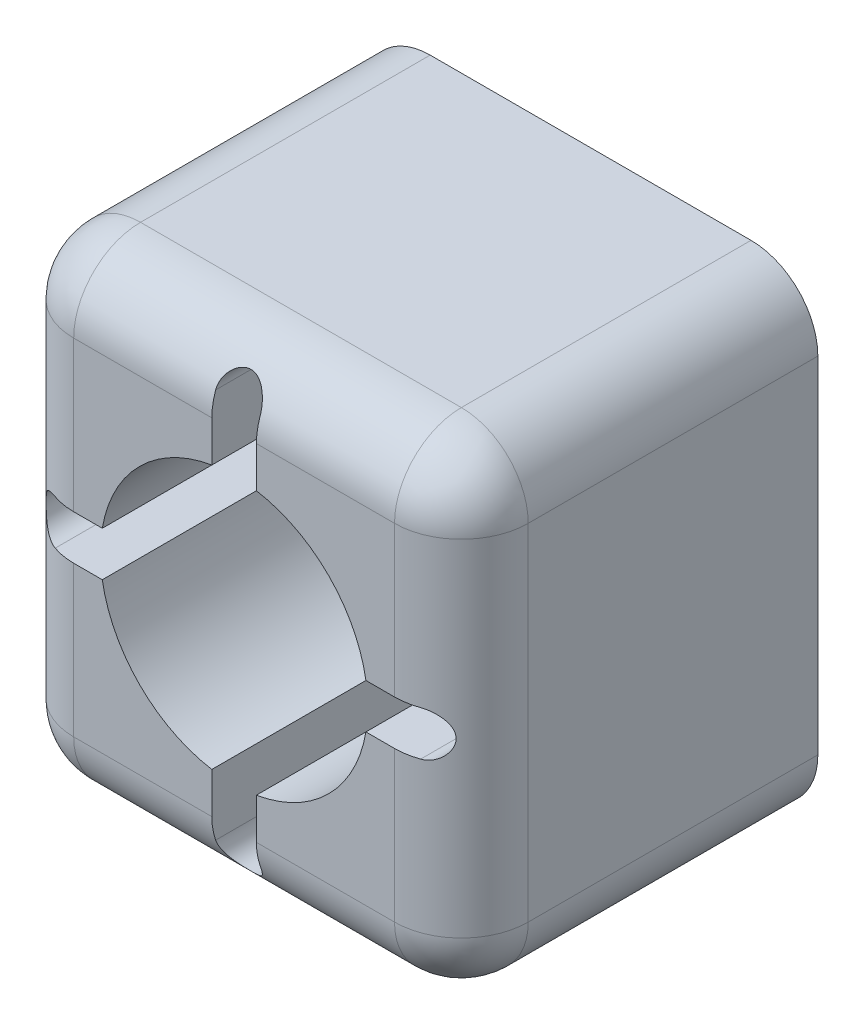
SolidWorks part; units mm, degrees
material "PVC Rigid"
ref_plane "Front Plane" through (0, 0, 0) normal (0, 0, 1) x (1, 0, 0)
ref_plane "Top Plane" through (0, 0, 0) normal (0, 1, 0) x (1, 0, 0)
ref_plane "Right Plane" through (0, 0, 0) normal (1, 0, 0) x (0, 0, -1)
ref_plane "Body alignment" through (0, 0, -6) normal (0, 0, 1) x (1, 0, 0)
ref_plane "Vertical center" through (10.2, 0, 0) normal (1, 0, 0) x (0, 0, -1)
ref_plane "Horizontal plane" through (0, 10.75, 0) normal (0, 1, 0) x (-1, 0, 0)
sketch "Sketch1" plane through (0, 0, 0) normal (0, 0, 1) x (1, 0, 0)
  line L1 (0, 0) -> (20.4, 0)
  line L2 (0, 0) -> (0, 21.5)
  line L3 (0, 21.5) -> (20.4, 21.5)
  line L4 (20.4, 0) -> (20.4, 21.5)
  dimension "D1" = 20.4
  dimension "D2" = 21.5
extrude "Extrude1" add sketch "Sketch1" against normal blind 16
sketch "Sketch11" plane through (0, 0, 0) normal (0, 0, 1) x (1, 0, 0)
  line L0 (10.2, -55) -> (10.2, 55) construction
  line L1 (0, 21.5) -> (20.4, 21.5) construction
  line L2 (0, 0) -> (0, 21.5) construction
  line L3 (20.4, 0) -> (20.4, 21.5) construction
  line L4 (2, 11.75) -> (4.2839, 11.75)
  line L5 (0, 0) -> (20.4, 0) construction
  line L6 (2, 9.75) -> (4.2839, 9.75)
  line L8 (9.2, 19.5) -> (9.2, 16.6661)
  line L10 (11.2, 19.5) -> (11.2, 16.6661)
  line L11 (16.1161, 11.75) -> (18.4, 11.75)
  line L13 (16.1161, 9.75) -> (18.4, 9.75)
  line L16 (9.2, 2) -> (9.2, 4.8339)
  line L18 (11.2, 2) -> (11.2, 4.8339)
  arc A0 (9.2, 16.6661) -> (4.2839, 11.75) centre (10.2, 10.75) ccw
  arc A1 (2, 9.75) -> (2, 11.75) centre (2, 10.75) cw
  arc A2 (11.2, 19.5) -> (9.2, 19.5) centre (10.2, 19.5) ccw
  arc A3 (18.4, 11.75) -> (18.4, 9.75) centre (18.4, 10.75) cw
  arc A4 (11.2, 2) -> (9.2, 2) centre (10.2, 2) cw
  arc A5 (4.2839, 9.75) -> (9.2, 4.8339) centre (10.2, 10.75) ccw
  arc A6 (16.1161, 11.75) -> (11.2, 16.6661) centre (10.2, 10.75) ccw
  arc A7 (11.2, 4.8339) -> (16.1161, 9.75) centre (10.2, 10.75) ccw
  dimension "D1" = 12
  dimension "D2" = 10.75
  dimension "D4" = 9.75
  dimension "D5" = 2
  dimension "D7" = 9.2
  dimension "D8" = 2
  dimension "D9" = 2
  dimension "D10" = 2
extrude "Extrude10" cut sketch "Sketch11" against normal blind 10
fillet "Fillet8" radius 3 8 edges at (20.4, 10.75, 0) (10.2, 0, 0) (0, 10.75, 0) (10.2, 21.5, 0) (20.4, 0, -8) (20.4, 21.5, -8) (0, 21.5, -8) (0, 0, -8)
ref_axis "Center axis" through (10.2, 10.75, 2.165) along (0, 0, -1)
